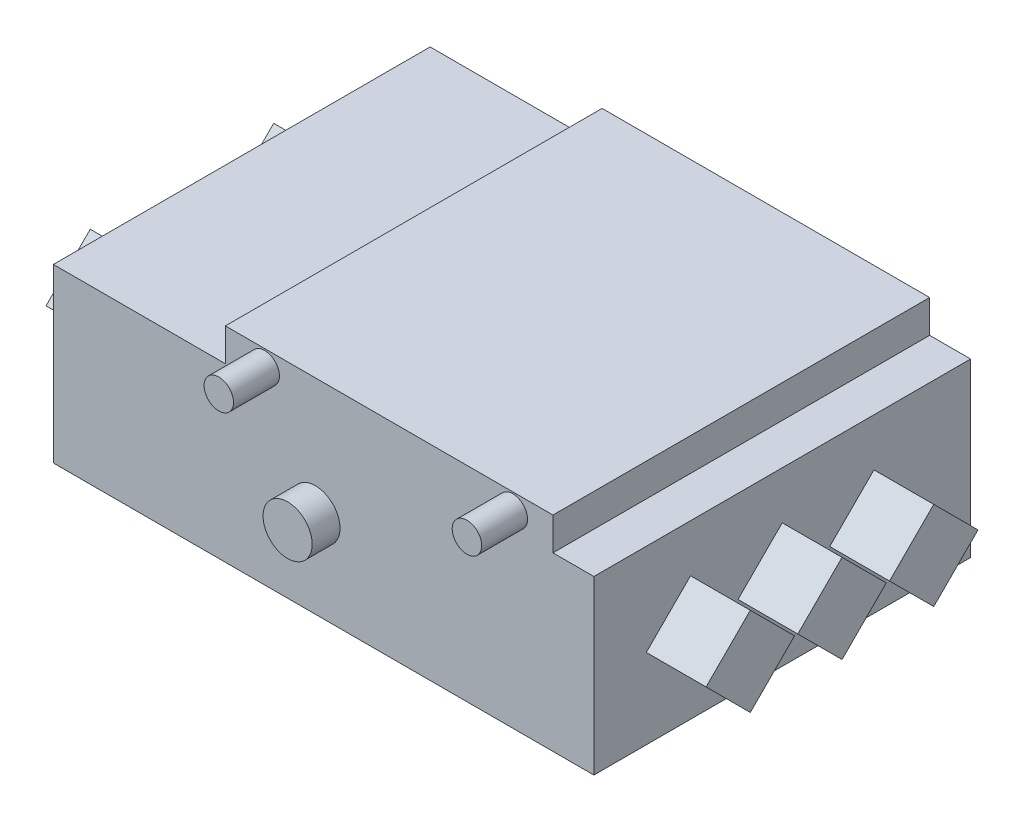
SolidWorks part; units mm, degrees
ref_plane "Front Plane" through (0, 0, 0) normal (0, 0, 1) x (1, 0, 0)
ref_plane "Top Plane" through (0, 0, 0) normal (0, 1, 0) x (1, 0, 0)
ref_plane "Right Plane" through (0, 0, 0) normal (1, 0, 0) x (0, 0, -1)
sketch "Sketch1" plane through (0, 0, 0) normal (0, 0, 1) x (1, 0, 0)
  line L1 (-165, 52.5) -> (165, 52.5)
  line L2 (-165, 52.5) -> (-165, -52.5)
  line L3 (-165, -52.5) -> (165, -52.5)
  line L4 (165, 52.5) -> (165, -52.5)
  line L5 (-165, 52.5) -> (165, -52.5) construction
  line L6 (-165, -52.5) -> (165, 52.5) construction
  point P0 (0, 0)
  dimension "D1" = 330
  dimension "D2" = 105
extrude "Boss-Extrude1" add sketch "Sketch1" along normal blind 230
sketch "Sketch2" plane through (0, 52.5, 0) normal (0, 1, 0) x (1, 0, 0)
  line L0 (165, 0) -> (-165, 0) construction
  line L1 (140, 0) -> (-60, 0)
  line L2 (140, 0) -> (140, -230)
  line L3 (140, -230) -> (-60, -230)
  line L4 (-60, 0) -> (-60, -230)
  line L5 (165, -230) -> (-165, -230) construction
  line L6 (165, -230) -> (165, 0) construction
  dimension "D1" = 200
  dimension "D2" = 25
extrude "Boss-Extrude2" add sketch "Sketch2" along normal blind 20
sketch "Sketch5" plane through (0, 0, 230) normal (0, 0, 1) x (1, 0, 0)
  line L0 (-60, 72.5) -> (140, 72.5) construction
  line L2 (165, -52.5) -> (165, 52.5) construction
  line L3 (165, 52.5) -> (140, 52.5) construction
  circle A0 centre (115.5, 62.5) radius 9
  circle A1 centre (-36, 62.5) radius 9
  circle A2 centre (-5, 0.5) radius 15
  circle A3 centre (-42.554, 0.5) radius 15.4192
  dimension "D1" = 18
  dimension "D2" = 18
  dimension "D6" = 30
  dimension "D3" = 10
  dimension "D4" = 49.5
  dimension "D5" = 201
  dimension "D7" = 170
  dimension "D8" = 52
extrude "Boss-Extrude4" add sketch "Sketch5" along normal blind 28 contours A0 | A1
extrude "Boss-Extrude5" add sketch "Sketch5<5>" along normal blind 17 contours A2 region at (-5, 0.5, 230)
sketch "Sketch5<5>" plane through (0, 0, 230) normal (0, 0, 1) x (1, 0, 0) same geometry as "Sketch5"
sketch "Sketch6" plane through (165, 0, 0) normal (1, 0, 0) x (0, 0, -1)
  line L0 (-86.0115, -3.6388) -> (-59, -30.6503)
  line L1 (-86.0115, -3.6388) -> (-59, 23.3727)
  line L2 (-59, -30.6503) -> (-31.9885, -3.6388)
  line L3 (-59, 23.3727) -> (-31.9885, -3.6388)
  line L4 (-86.0115, -3.6388) -> (-31.9885, -3.6388) construction
  line L5 (-59, -30.6503) -> (-59, 23.3727) construction
  line L6 (-230, -52.5) -> (0, -52.5) construction
  line L8 (-142.0115, -3.6388) -> (-115, -30.6503)
  line L9 (-142.0115, -3.6388) -> (-115, 23.3727)
  line L10 (-115, 23.3727) -> (-87.9885, -3.6388)
  line L11 (-115, -30.6503) -> (-87.9885, -3.6388)
  line L12 (-198.0115, -3.6388) -> (-171, -30.6503)
  line L13 (-198.0115, -3.6388) -> (-171, 23.3727)
  line L14 (-171, 23.3727) -> (-143.9885, -3.6388)
  line L15 (-171, -30.6503) -> (-143.9885, -3.6388)
  point P1 (-59, -3.6388)
  point P3 (-171, -3.6388)
  point P10 (-115, -3.6388)
  dimension "D1" = 59
  dimension "D2" = 57.1694
  dimension "D3" = 45
  dimension "D4" = 38.2
  dimension "D5" = 38.2
  dimension "D6" = 3
extrude "Boss-Extrude6" add sketch "Sketch6" along normal blind 36.5
mirror "Mirror1" about plane through (0, 0, 0) normal (1, 0, 0) of face at (183.25, -17.1445, 72.5057) of face at (201.5, -3.6388, 59) of face at (183.25, -17.1445, 45.4943) of face at (183.25, 9.8669, 45.4943) of face at (183.25, 9.8669, 72.5057) of face at (183.25, 9.8669, 157.4943) of face at (201.5, -3.6388, 171) of face at (183.25, -17.1445, 157.4943) of face at (183.25, -17.1445, 184.5057) of face at (183.25, 9.8669, 184.5057)
sketch "Sketch7" plane through (201.5, 0, 0) normal (1, 0, 0) x (0, 0, -1)
  point P0 (-59, -3.6388)
ref_plane "Mid plane" through (0, 0, 0) normal (1, 0, 0) x (0, 0, -1)
